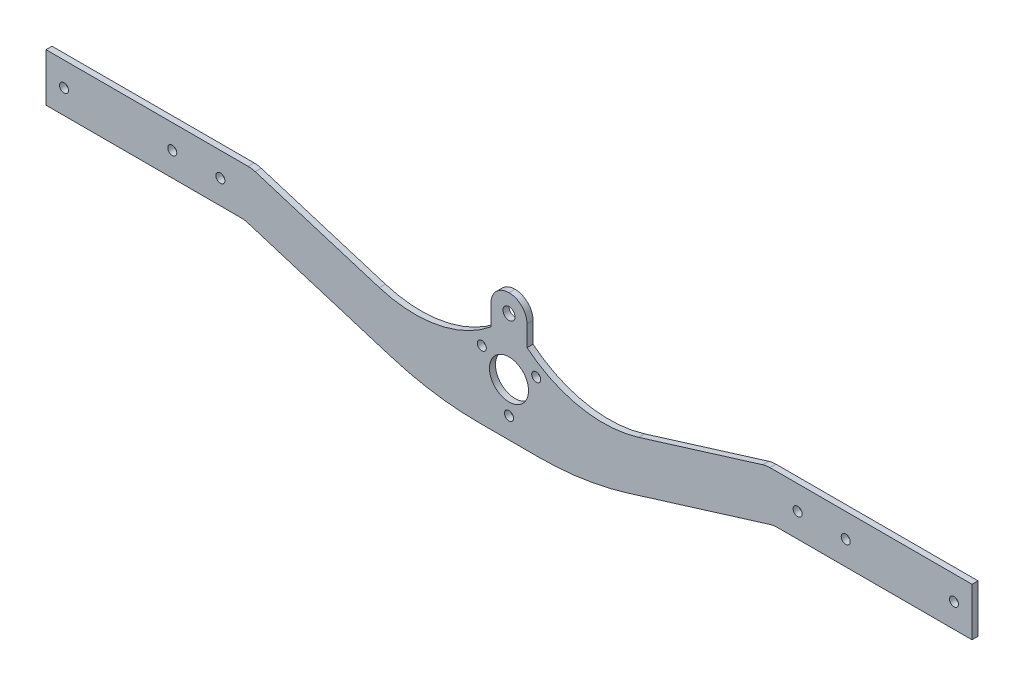
SolidWorks part; units mm, degrees
ref_plane "Спереди" through (0, 0, 0) normal (0, 0, 1) x (1, 0, 0)
ref_plane "Сверху" through (0, 0, 0) normal (0, 1, 0) x (1, 0, 0)
ref_plane "Справа" through (0, 0, 0) normal (1, 0, 0) x (0, 0, -1)
sketch "Эскиз Петрушки" plane through (0, 0, 0) normal (0, 0, 1) x (1, 0, 0)
  line L0 (0, 0) -> (0, -24) construction
  line L1 (0, 0) -> (130, 10) construction
  line L2 (148, 10) -> (96, 10) construction
  line L4 (130, -76) -> (-130, -76) construction
  line L6 (130, 10) -> (130, -76) construction
  line L8 (-130, 10) -> (-130, -76) construction
  line L9 (-130, -76) -> (130, -76) construction
  line L10 (-148, 10) -> (-96, 10) construction
  line L11 (0, 0) -> (-130, 10) construction
  circle A0 centre (0, 19) radius 2
  circle A1 centre (130, -76) radius 57.5 construction
  circle A3 centre (148, 10) radius 1.5
  circle A4 centre (112, 10) radius 1.5
  circle A5 centre (96, 10) radius 1.5
  circle A6 centre (-130, -76) radius 57.5 construction
  circle A7 centre (-96, 10) radius 1.5
  circle A8 centre (-112, 10) radius 1.5
  circle A9 centre (-148, 10) radius 1.5
  circle A10 centre (0, 0) radius 3
  dimension "D1" = 4
  dimension "D2" = 19
  dimension "D3" = 10
  dimension "D4" = 3
  dimension "D5" = 130
  dimension "D10" = 115
  dimension "D11" = 6
  dimension "D6" = 86
  dimension "D7" = 18
  dimension "D8" = 18
  dimension "D9" = 34
sketch "Эскиз8" plane through (0, 0, 0) normal (0, 0, 1) x (1, 0, 0)
  line L0 (43.1288, 4.8921) -> (85.5864, 18)
  line L1 (85.5864, 18) -> (154, 18)
  line L2 (154, 18) -> (154, 2)
  line L3 (154, 2) -> (88, 2)
  line L5 (-12.7222, 2.951) -> (-10.3652, -3.6828) construction
  line L10 (90, 18) -> (90, 2) construction
  line L12 (-8.9167, 9.5422) -> (-1.9932, 10.8179) construction
  line L13 (3.8054, -12.4932) -> (8.372, -7.1351) construction
  line L14 (-3.8054, -12.4932) -> (-8.372, -7.1351) construction
  line L15 (0, -10.45) -> (0, 0) construction
  line L17 (0, 0) -> (-8.0107, 4.625) construction
  line L18 (8.9167, 9.5422) -> (1.9932, 10.8179) construction
  line L19 (0, 0) -> (8.0107, 4.625) construction
  line L20 (6, 25) -> (-6, 25)
  line L21 (88, 2) -> (25, -17.45)
  line L23 (12.7222, 2.951) -> (10.3652, -3.6828) construction
  line L26 (6, 12.1534) -> (6, 25)
  line L29 (43.1288, 4.8921) -> (9.7505, -5.4128) construction
  line L30 (6, 12.1534) -> (6, 10.0796) construction
  line L31 (-6, 12.1534) -> (-6, 25)
  line L32 (-43.1288, 4.8921) -> (-85.5864, 18)
  line L33 (-88, 2) -> (-25, -17.45)
  line L34 (-154, 2) -> (-88, 2)
  line L35 (-154, 18) -> (-154, 2)
  line L36 (-85.5864, 18) -> (-154, 18)
  line L37 (-25, -17.45) -> (25, -17.45)
  circle A2 centre (0, 0) radius 6.5
  circle A3 centre (0, 0) radius 11 construction
  arc A4 (-8.9167, 9.5422) -> (-12.7222, 2.951) centre (-8.0107, 4.625) ccw construction
  arc A5 (1.9932, 10.8179) -> (-1.9932, 10.8179) centre (0, 0) ccw construction
  arc A6 (-3.8054, -12.4932) -> (3.8054, -12.4932) centre (0, -9.25) ccw construction
  arc A7 (12.7222, 2.951) -> (8.9167, 9.5422) centre (8.0107, 4.625) ccw construction
  arc A8 (8.372, -7.1351) -> (10.3652, -3.6828) centre (0, 0) ccw construction
  arc A9 (-8.372, -7.1351) -> (-10.3652, -3.6828) centre (0, 0) cw construction
  circle A10 centre (0, 0) radius 9.25 construction
  circle A11 centre (0, -10.45) radius 1.5
  circle A14 centre (0, 0) radius 7.65 construction
  circle A15 centre (148, 10) radius 1.5
  circle A16 centre (96, 10) radius 1.5
  circle A17 centre (0, 19) radius 2
  circle A21 centre (112, 10) radius 1.5
  circle A22 centre (-9.05, 5.225) radius 1.5
  circle A23 centre (9.05, 5.225) radius 1.5
  circle A24 centre (0, 19) radius 2 construction
  circle A25 centre (112, 10) radius 1.5 construction
  circle A26 centre (96, 10) radius 1.5 construction
  circle A27 centre (148, 10) radius 1.5 construction
  arc A28 (6, 12.1534) -> (43.1288, 4.8921) centre (31.3291, 43.1121) ccw
  arc A29 (-6, 12.1534) -> (-43.1288, 4.8921) centre (-31.3291, 43.1121) cw
  circle A30 centre (-112, 10) radius 1.5
  circle A31 centre (-96, 10) radius 1.5
  circle A32 centre (-148, 10) radius 1.5
  point P6 (154, 10)
  point P25 (0, 25)
  point P49 (0, 0)
  point P53 (0, 0)
  point P63 (0, -17.45)
  point P70 (0, 0)
  dimension "D2" = 13
  dimension "D3" = 5
  dimension "D4" = 18.5
  dimension "D5" = 22
  dimension "D6" = 3
  dimension "D7" = 15.3
  dimension "D15" = 7
  dimension "D16" = 40
  dimension "D1" = 16
  dimension "D8" = 10.45
  dimension "D9" = 12
  dimension "D10" = 120
  dimension "D11" = 120
  dimension "D12" = 6
  dimension "D13" = 16
  dimension "D14" = 2
  dimension "D17" = 50
  dimension "D18" = 6
  dimension "D22" = 6
  dimension "D20" = 3
extrude "Арка Петрушки" add sketch "Эскиз8" along normal blind 2
fillet "Скругление27" radius 6 2 edges at (-6, 25, 1) (6, 25, 1)
fillet "Скругление28" radius 8 4 edges at (-88, 2, 1) (-85.5864, 18, 1) (88, 2, 1) (85.5864, 18, 1)
fillet "Скругление29" radius 100 2 edges at (25, -17.45, 1) (-25, -17.45, 1)
